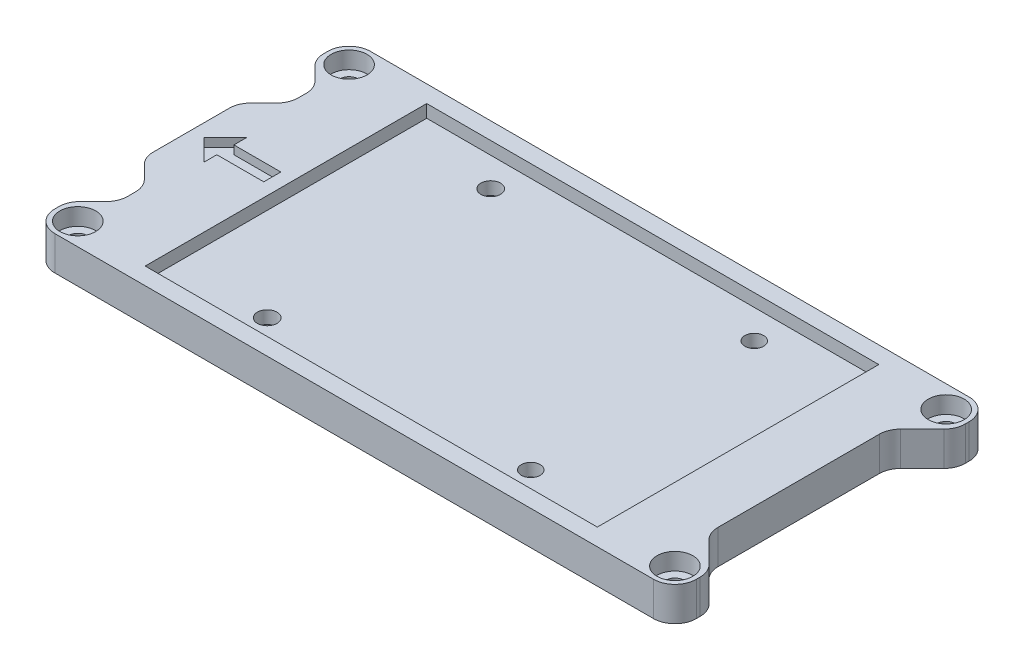
SolidWorks part; units mm, degrees
ref_plane "Płaszczyzna przednia" through (0, 0, 0) normal (0, 0, 1) x (1, 0, 0)
ref_plane "Płaszczyzna górna" through (0, 0, 0) normal (0, 1, 0) x (1, 0, 0)
ref_plane "Płaszczyzna prawa" through (0, 0, 0) normal (1, 0, 0) x (0, 0, -1)
sketch "Szkic1" plane through (0, 0, 0) normal (0, 1, 0) x (1, 0, 0)
  line L1 (-37.6, -18.5) -> (37.6, -18.5)
  line L2 (-37.6, -18.5) -> (-37.6, 18.5)
  line L3 (-37.6, 18.5) -> (37.6, 18.5)
  line L4 (37.6, -18.5) -> (37.6, 18.5)
  line L5 (-37.6, -18.5) -> (37.6, 18.5) construction
  line L6 (-37.6, 18.5) -> (37.6, -18.5) construction
  point P0 (0, 0)
  dimension "D1" = 75.2
  dimension "D2" = 37
extrude "Dodanie-wyciągnięcie1" add sketch "Szkic1" along normal blind 4
sketch "Szkic2" plane through (0, 4, 0) normal (0, 1, 0) x (1, 0, 0)
  line L1 (-26.5, -16.5) -> (26.5, -16.5)
  line L2 (-26.5, -16.5) -> (-26.5, 16.5)
  line L3 (-26.5, 16.5) -> (26.5, 16.5)
  line L4 (26.5, -16.5) -> (26.5, 16.5)
  line L5 (-26.5, -16.5) -> (26.5, 16.5) construction
  line L6 (-26.5, 16.5) -> (26.5, -16.5) construction
  point P0 (0, 0)
  dimension "D1" = 53
  dimension "D2" = 33
extrude "Wytnij-wyciągnięcie1" cut sketch "Szkic2" against normal blind 1.5
sketch "Szkic4" plane through (0, 4, 0) normal (0, 1, 0) x (1, 0, 0)
  line L0 (0, 0) -> (-35, 0) construction
  line L2 (-35, 0) -> (-35, 15.9) construction
  circle A1 centre (-35, 15.9) radius 1.1
  dimension "D1" = 35
  dimension "D3" = 2.2
  dimension "D2" = 15.9
extrude "Wytnij-wyciągnięcie2" cut sketch "Szkic4" against normal through all
sketch "Szkic8" plane through (0, 4, 0) normal (0, 1, 0) x (1, 0, 0)
  circle A0 centre (-35, 15.9) radius 2.1
  dimension "D1" = 4.2
extrude "Wytnij-wyciągnięcie5" cut sketch "Szkic8" against normal blind 2
mirror "Lustro1" about plane through (0, 0, 0) normal (0, 0, 1) of "Wytnij-wyciągnięcie5", "Wytnij-wyciągnięcie2"
mirror "Lustro2" about plane through (0, 0, 0) normal (1, 0, 0) of "Lustro1"
fillet "Zaokrąglenie1" radius 2.5 4 edges at (-37.6, 2, 18.5) (-37.6, 2, -18.5) (37.6, 2, -18.5) (37.6, 2, 18.5)
sketch "Szkic6" plane through (0, 2.5, 0) normal (0, 1, 0) x (1, 0, 0)
  line L0 (26.5, -16.5) -> (26.5, -13.1) construction
  line L1 (26.5, -16.5) -> (26.5, 16.5) construction
  line L2 (26.5, -13.1) -> (15.3, -13.1) construction
  line L3 (-26.5, -16.5) -> (-26.5, -13.1) construction
  line L4 (-26.5, 16.5) -> (-26.5, -16.5) construction
  line L5 (-26.5, -13.1) -> (-15.6, -13.1) construction
  circle A0 centre (-15.6, -13.1) radius 1.15
  circle A1 centre (15.3, -13.1) radius 1.1
  dimension "D5" = 2.3
  dimension "D6" = 2.2
  dimension "D1" = 3.4
  dimension "D2" = 11.2
  dimension "D3" = 10.9
  dimension "D4" = 3.4
extrude "Wytnij-wyciągnięcie3" cut sketch "Szkic6" against normal through all
sketch "Szkic11" plane through (0, 0, 0) normal (0, -1, 0) x (1, 0, 0)
  line L0 (-15.6, 13.1) -> (15.3, 13.1) construction
  line L1 (-0.15, 13.1) -> (-0.15, 9.4495) construction
  circle A0 centre (15.3, 13.1) radius 2.1
  circle A1 centre (-15.6, 13.1) radius 2.1
  dimension "D1" = 4.2
extrude "Wytnij-wyciągnięcie8" cut sketch "Szkic11" against normal blind 1
mirror "Lustro3" about plane through (0, 0, 0) normal (0, 0, 1) of "Wytnij-wyciągnięcie8", "Wytnij-wyciągnięcie3"
sketch "Szkic7" plane through (0, 4, 0) normal (0, 1, 0) x (1, 0, 0)
  line L0 (-37.6, 0) -> (-36.1, 0) construction
  line L1 (-37.6, 16) -> (-37.6, -16) construction
  line L2 (-36.1, 0) -> (-33.6, 2.5)
  line L3 (-33.6, 2.5) -> (-33.6, 1)
  line L4 (-33.6, 1) -> (-28.1, 1)
  line L5 (-28.1, 1) -> (-28.1, -1)
  line L6 (-33.6, -1) -> (-28.1, -1)
  line L7 (-36.1, 0) -> (-33.6, -2.5)
  line L8 (-33.6, -2.5) -> (-33.6, -1)
  point P11 (-28.1, 0)
  dimension "D1" = 1.5
  dimension "D2" = 5
  dimension "D3" = 45
  dimension "D4" = 8
  dimension "D5" = 2
extrude "Wytnij-wyciągnięcie4" cut sketch "Szkic7" against normal blind 1
sketch "Szkic9" plane through (0, 4, 0) normal (0, 1, 0) x (1, 0, 0)
  line L0 (-37.6, 16) -> (-37.6, 14.5) construction
  line L1 (-37.6, 16) -> (-37.6, -16) construction
  line L2 (-37.6, 14.5) -> (-34.6, 11.5)
  line L3 (-34.6, 11.5) -> (-34.6, 8.5)
  line L4 (-34.6, 8.5) -> (-37.6, 5.5)
  line L5 (-37.6, 5.5) -> (-37.6, 0) construction
  line L6 (-37.6, 5.5) -> (-37.6, 14.5)
  point P5 (-37.6, 10)
  point P10 (-37.6, 6.3386)
  dimension "D1" = 6
  dimension "D2" = 3
  dimension "D3" = 45
  dimension "D4" = 45
  dimension "D5" = 3
extrude "Wytnij-wyciągnięcie6" cut sketch "Szkic9" against normal through all
fillet "Zaokrąglenie2" radius 2.5 4 edges at (-37.6, 2, -5.5) (-34.6, 2, -8.5) (-34.6, 2, -11.5) (-37.6, 2, -14.5)
mirror "Lustro4" about plane through (0, 0, 0) normal (0, 0, 1) of "Wytnij-wyciągnięcie6", "Zaokrąglenie2"
sketch "Szkic10" plane through (0, 4, 0) normal (0, 1, 0) x (1, 0, 0)
  line L0 (37.6, 16) -> (37.6, 14.5) construction
  line L1 (37.6, -16) -> (37.6, 16) construction
  line L2 (37.6, 14.5) -> (33.6, 10.5)
  line L3 (37.6, 14.5) -> (37.6, -14.5)
  line L4 (37.6, 0) -> (33.6, 0) construction
  line L5 (33.6, -10.5) -> (33.6, 10.5)
  line L6 (37.6, -14.5) -> (33.6, -10.5)
  dimension "D1" = 1.5
  dimension "D2" = 45
  dimension "D3" = 4
extrude "Wytnij-wyciągnięcie7" cut sketch "Szkic10" against normal through all
fillet "Zaokrąglenie3" radius 2.5 4 edges at (37.6, 2, 14.5) (33.6, 2, 10.5) (33.6, 2, -10.5) (37.6, 2, -14.5)
